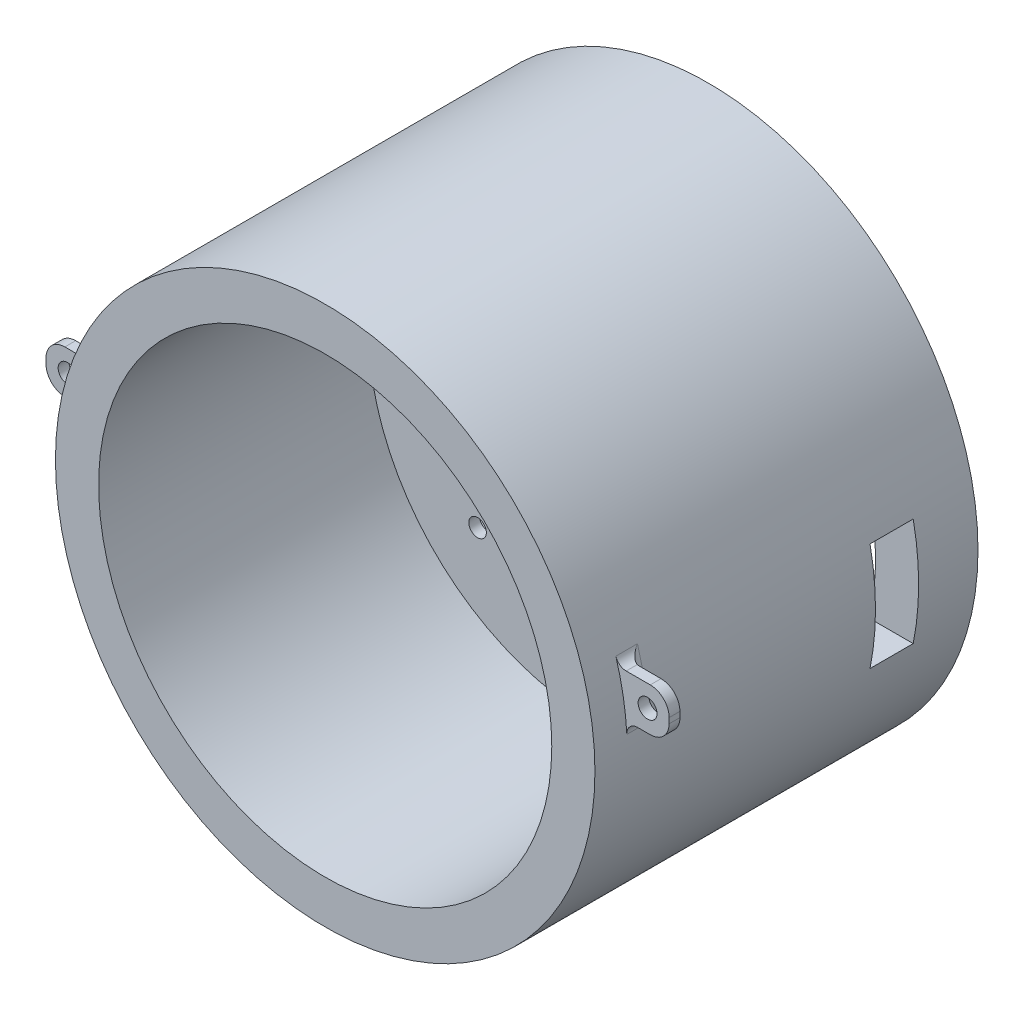
SolidWorks part; units mm, degrees
other "Marquage1"
sketch "Esquisse7" plane through (-50, 50, 23) normal (-0.1287, 0.8674, 0.4808) x (0.986, 0.1637, -0.0313)
ref_plane "Plan de face" through (0, 0, 0) normal (0, 0, 1) x (1, 0, 0)
ref_plane "Plan de dessus" through (0, 0, 0) normal (0, 1, 0) x (1, 0, 0)
ref_plane "Plan de droite" through (0, 0, 0) normal (1, 0, 0) x (0, 0, -1)
sketch "Esquisse1" plane through (0, 0, 0) normal (0, 0, 1) x (1, 0, 0)
  circle A3 centre (0, 0) radius 50
  dimension "D1" = 100
extrude "Boss.-Extru.1" add sketch "Esquisse1" along normal blind 71
shell "Coque1" thickness 8 removed face at (50, 0, 71)
sketch "Esquisse2" plane through (0, 0, 71) normal (0, 0, 1) x (1, 0, 0)
  line L1 (-21.75, 21.75) -> (21.75, 21.75) construction
  line L2 (-21.75, 21.75) -> (-21.75, -21.75) construction
  line L3 (-21.75, -21.75) -> (21.75, -21.75) construction
  line L4 (21.75, 21.75) -> (21.75, -21.75) construction
  line L5 (-27.5, 27.5) -> (27.5, 27.5) construction
  line L6 (-27.5, 27.5) -> (-27.5, -27.5) construction
  line L7 (-27.5, -27.5) -> (27.5, -27.5) construction
  line L8 (27.5, 27.5) -> (27.5, -27.5) construction
  circle A0 centre (0, 0) radius 42
  circle A2 centre (-21.75, 21.75) radius 1.625
  circle A3 centre (21.75, 21.75) radius 1.625
  circle A4 centre (21.75, -21.75) radius 1.625
  circle A5 centre (-21.75, -21.75) radius 1.625
  circle A6 centre (0, 0) radius 42 construction
  point P9 (0, 21.75)
  point P10 (-21.75, 0)
  point P19 (0, 27.5)
  point P20 (-27.5, 0)
  circle M1 centre (0, 0) radius 42
  dimension "D2" = 3.25
  dimension "D1" = 43.5
  dimension "D3" = 55
extrude "Enlèv. mat.-Extru.4" cut sketch "Esquisse2" against normal up to surface (71 mm away) contours A3 | A4 | A5 | A2 | A5 A4 A3 A2 M1 region at (0, 0, 71) region at (-21.75, 21.75, 71) region at (21.75, 21.75, 71) region at (21.75, -21.75, 71) region at (-21.75, -21.75, 71) up to face at (50, 0, 0)
extrude "Boss.-Extru.4" add sketch "Esquisse2<5>" against normal blind 52 contours A5 A4 A3 A2 M1 | A2 | A3 | A4 | A5 region at (0, 0, 71) region at (-21.75, 21.75, 71) region at (21.75, 21.75, 71) region at (21.75, -21.75, 71) region at (-21.75, -21.75, 71)
sketch "Esquisse2<5>" plane through (0, 0, 71) normal (0, 0, 1) x (1, 0, 0) same geometry as "Esquisse2"
extrude "Enlèv. mat.-Extru.5" cut sketch "Esquisse2<6>" against normal blind 50
sketch "Esquisse2<6>" plane through (0, 0, 71) normal (0, 0, 1) x (1, 0, 0) same geometry as "Esquisse2"
extrude "Enlèv. mat.-Extru.6" cut sketch "Esquisse2<7>" against normal up to next contours A2 | A3 | A4 | A5 region at (-21.75, 21.75, 71) region at (21.75, 21.75, 71) region at (21.75, -21.75, 71) region at (-21.75, -21.75, 71)
sketch "Esquisse2<7>" plane through (0, 0, 71) normal (0, 0, 1) x (1, 0, 0) same geometry as "Esquisse2"
ref_plane "Plan1" through (50, 0, 0) normal (1, 0, 0) x (0, 0, -1)
sketch "Esquisse9" plane through (50, 0, 0) normal (1, 0, 0) x (0, 0, -1)
  line L0 (-19, 0) -> (0, 0) construction
  line L2 (-11, -10) -> (-19, -10)
  line L3 (-11, -10) -> (-11, 10)
  line L4 (-11, 10) -> (-19, 10)
  line L5 (-19, -10) -> (-19, 10)
  point P7 (-11, 0)
  dimension "D1" = 19
  dimension "D3" = 20
  dimension "D4" = 8
extrude "Enlèv. mat.-Extru.7" cut sketch "Esquisse9" against normal up to next
ref_plane "Plan3" through (0, 0, 65) normal (0, 0, 1) x (1, 0, 0)
sketch "Esquisse14" plane through (0, 0, 65) normal (0, 0, 1) x (1, 0, 0)
  line L0 (50, 0) -> (42, 0) construction
  line L1 (46, 0) -> (46, 9) construction
  line L2 (46, 9) -> (53.7494, 9) construction
  line L3 (49.7494, 5) -> (57.7494, 5)
  line L4 (57.7494, 5) -> (57.7494, 13)
  line L5 (57.7494, 13) -> (48.2804, 13)
  circle A0 centre (0, 0) radius 50 construction
  circle A2 centre (0, 0) radius 42 construction
  circle A3 centre (53.7494, 9) radius 1.75
  arc A4 (49.7494, 5) -> (48.2804, 13) centre (0, 0) ccw
  point P16 (53.7494, 5)
  point P18 (57.7494, 9)
  dimension "D2" = 3.5
  dimension "D1" = 9
  dimension "D4" = 8
extrude "Boss.-Extru.6" add sketch "Esquisse14" against normal blind 2 contours L0 | A4 L3 L4 L5 A3 region at (49.2998, 9.0523, 65)
mirror "Symétrie1" about plane through (0, 0, 0) normal (1, 0, 0) of "Boss.-Extru.6"
fillet "Congé1" radius 2 6 edges at (-48.2804, 13, 64) (-49.1778, 9.0299, 63) (-49.7494, 5, 64) (48.2804, 13, 64) (49.7494, 5, 64) (49.1778, 9.0299, 63)
fillet "Congé2" radius 3.5 4 edges at (57.7494, 13, 64) (57.7494, 5, 64) (-57.7494, 5, 64) (-57.7494, 13, 64)
